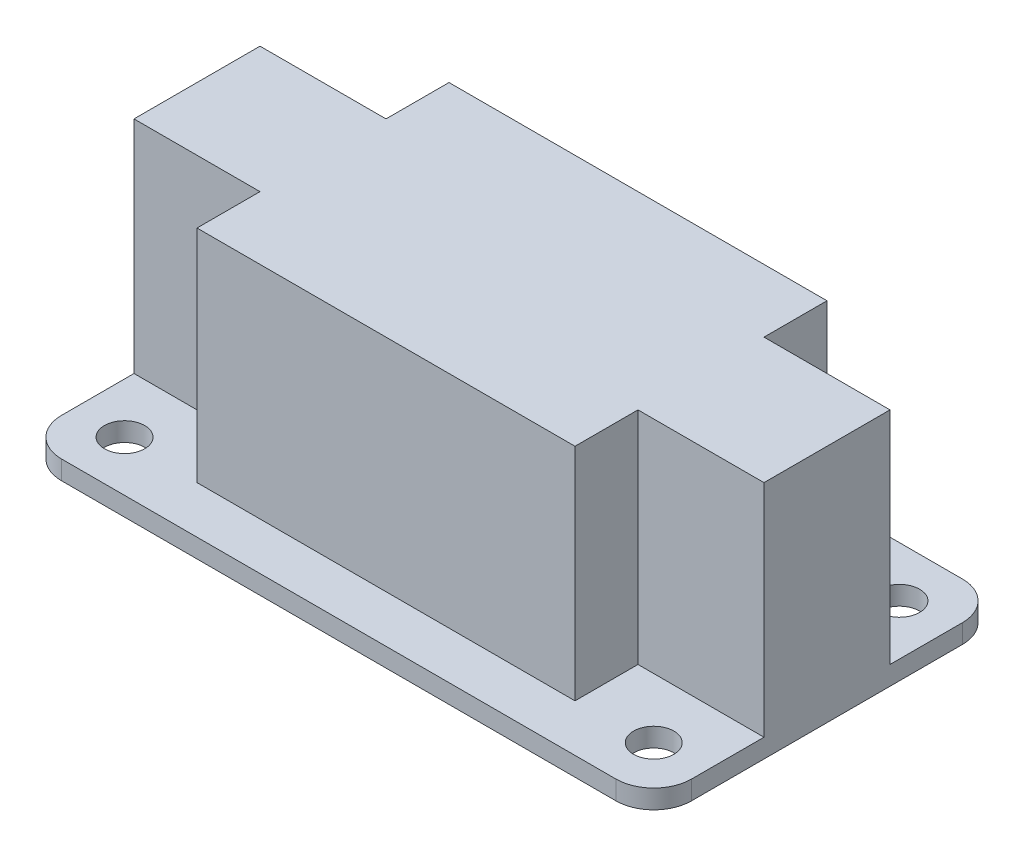
SolidWorks part; units mm, degrees
ref_plane "Front Plane" through (0, 0, 0) normal (0, 0, 1) x (1, 0, 0)
ref_plane "Top Plane" through (0, 0, 0) normal (0, 1, 0) x (1, 0, 0)
ref_plane "Right Plane" through (0, 0, 0) normal (1, 0, 0) x (0, 0, -1)
sketch "Sketch2" plane through (0, 0, 0) normal (0, 1, 0) x (1, 0, 0)
  line L0 (25, 27.5) -> (25, 0) construction
  line L1 (0, 0) -> (50, 0)
  line L2 (0, 0) -> (0, 27.5)
  line L3 (0, 27.5) -> (50, 27.5)
  line L4 (50, 0) -> (50, 27.5)
  line L5 (0, 13.75) -> (50, 13.75) construction
  line L7 (4, 4) -> (46, 4)
  line L8 (4, 4) -> (4, 23.5)
  line L9 (4, 23.5) -> (46, 23.5)
  line L10 (46, 4) -> (46, 23.5)
  line L11 (4, 4) -> (46, 23.5) construction
  line L12 (4, 23.5) -> (46, 4) construction
  circle A0 centre (46, 23.5) radius 1.6
  circle A1 centre (46, 4) radius 1.6
  circle A2 centre (4, 23.5) radius 1.6
  circle A3 centre (4, 4) radius 1.6
  point P9 (25, 13.75)
  dimension "D5" = 3.2
  dimension "D6" = 3.2
  dimension "D7" = 3.2
  dimension "D8" = 3.2
  dimension "D1" = 50
  dimension "D2" = 27.5
  dimension "D3" = 4
  dimension "D4" = 4
extrude "Boss-Extrude1" add sketch "Sketch2" along normal blind 1.5 contours L1 L4 L3 L2 A3 L8 A2 L9 A0 L10 A1 L7 | A3 L7 A1 L10 A0 L9 A2 L8 region at (0.5706, 0, -13.75) region at (25, 0, -13.75)
fillet "Fillet1" radius 3 4 edges at (0, 0.75, -27.5) (0, 0.75, 0) (50, 0.75, -27.5) (50, 0.75, 0)
sketch "Sketch3" plane through (0, 0, 0) normal (0, 1, 0) x (1, 0, 0)
  line L0 (0, 13.75) -> (50, 13.75) construction
  line L5 (0, 3) -> (0, 24.5) construction
  line L6 (50, 3) -> (50, 24.5) construction
  line L8 (10, 8.75) -> (0, 8.75)
  line L9 (10, 8.75) -> (10, 18.75)
  line L10 (10, 18.75) -> (0, 18.75)
  line L11 (0, 8.75) -> (0, 18.75)
  line L12 (10, 8.75) -> (0, 18.75) construction
  line L13 (10, 18.75) -> (0, 8.75) construction
  line L14 (40, 3.75) -> (10, 3.75)
  line L15 (40, 3.75) -> (40, 23.75)
  line L16 (40, 23.75) -> (10, 23.75)
  line L17 (10, 3.75) -> (10, 23.75)
  line L18 (40, 3.75) -> (10, 23.75) construction
  line L19 (40, 23.75) -> (10, 3.75) construction
  line L20 (40, 8.75) -> (50, 8.75)
  line L21 (40, 8.75) -> (40, 18.75)
  line L22 (40, 18.75) -> (50, 18.75)
  line L23 (50, 8.75) -> (50, 18.75)
  line L24 (40, 8.75) -> (50, 18.75) construction
  line L25 (40, 18.75) -> (50, 8.75) construction
  point P0 (5, 13.75)
  point P11 (25, 13.75)
  point P16 (45, 13.75)
  point P21 (40, 8.7851)
  dimension "D1" = 10
  dimension "D2" = 10
  dimension "D3" = 30
  dimension "D4" = 20
  dimension "D5" = 10
extrude "Boss-Extrude2" add sketch "Sketch3" along normal blind 19 contours L11 L8 L9 L10 | L17 L14 L15 L16 L9 | L20 L23 L22 L15 region at (5, 0, -13.75) region at (25, 0, -13.75) region at (45, 0, -13.75)
